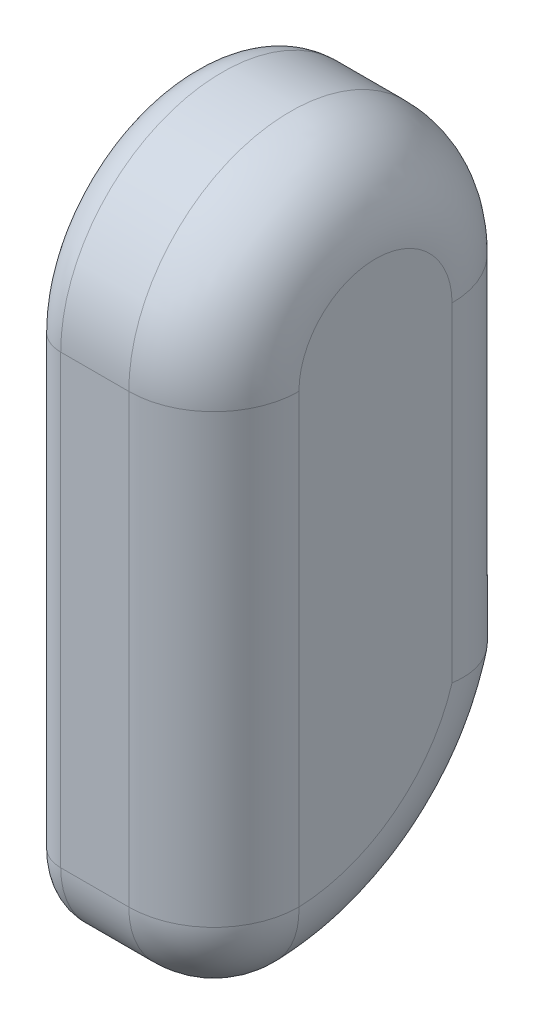
SolidWorks part; units mm, degrees
ref_plane "Plano frontal" through (0, 0, 0) normal (0, 0, 1) x (1, 0, 0)
ref_plane "Plano superior" through (0, 0, 0) normal (0, 1, 0) x (1, 0, 0)
ref_plane "Plano direito" through (0, 0, 0) normal (1, 0, 0) x (0, 0, -1)
sketch "Esboço1" plane through (0, 0, 0) normal (1, 0, 0) x (0, 0, -1)
  line L1 (9.5, 0) -> (9.5, -20)
  line L2 (-9.5, 0) -> (-9.5, -30.5)
  circle A0 centre (0, 0) radius 9.5
  arc A1 (9.5, -20) -> (-9.5, -30.5) centre (-4.8455, -16.482) cw
  dimension "D1" = 19
  dimension "D2" = 30.5
  dimension "D3" = 14.7705
  dimension "D4" = 20
extrude "Ressalto-extrusão1" add sketch "Esboço1" against normal blind 11 contours A0 | A1 L1 A0 L2 region at (0, 0, 0) region at (0, -18.3094, 0.6089)
fillet "Filete1" radius 5 1 edges at (-5.5, -30.5, 9.5)
sketch "Esboço2" plane through (0, 0, 0) normal (1, 0, 0) x (0, 0, -1)
  circle A0 centre (0, 0) radius 5.1
  dimension "D1" = 10.2
extrude "Corte-extrusão1" cut sketch "Esboço2" against normal blind 6 from offset 5 offset against normal yes
fillet "Filete5" radius 2 5 edges at (-11, 9.5, 0) (-11, -10, -9.5) (-11, -27.9408, -4.4747) (-11, -29.8439, 7.9725) (-11, -13.1232, 9.5)
fillet "Filete6" radius 5 5 edges at (0, 9.5, 0) (0, -10, -9.5) (0, -27.9408, -4.4747) (0, -29.8439, 7.9725) (0, -13.1232, 9.5)
